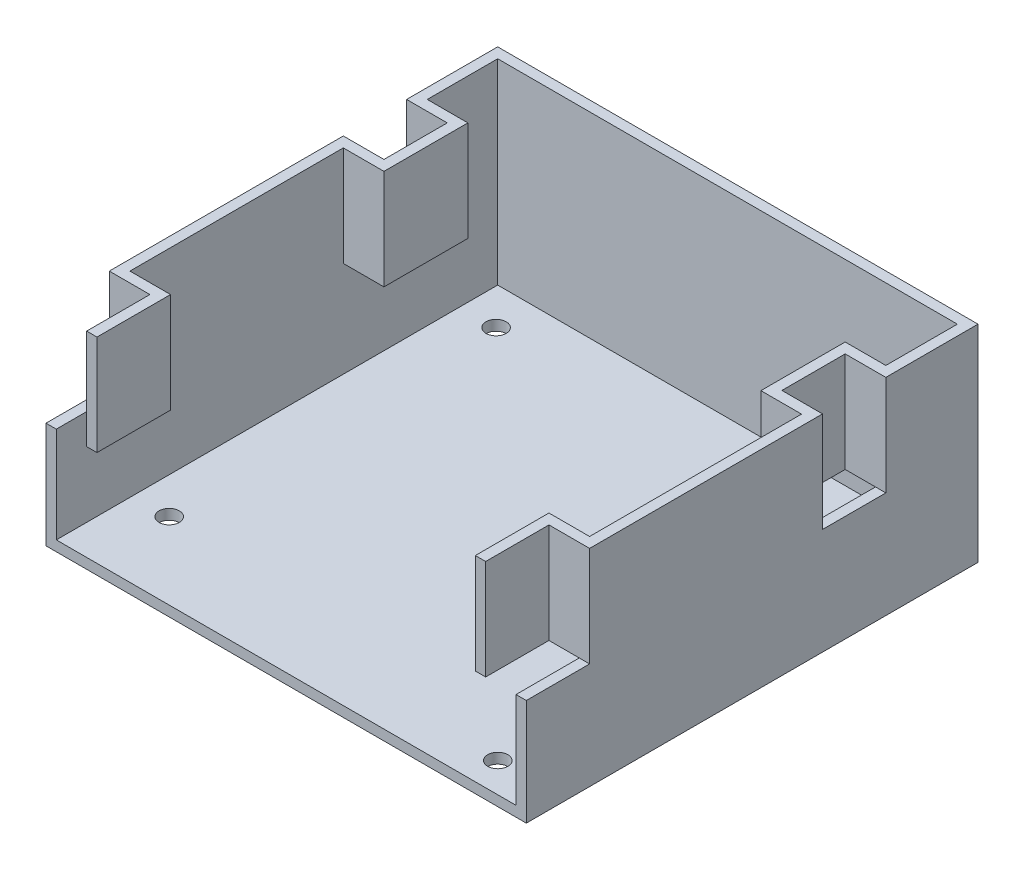
SolidWorks part; units mm, degrees
ref_plane "Front Plane" through (0, 0, 0) normal (0, 0, 1) x (1, 0, 0)
ref_plane "Top Plane" through (0, 0, 0) normal (0, 1, 0) x (1, 0, 0)
ref_plane "Right Plane" through (0, 0, 0) normal (1, 0, 0) x (0, 0, -1)
sketch "Sketch1" plane through (0, 0, 0) normal (0, 1, 0) x (1, 0, 0)
  line L1 (0, 0) -> (89.12, 0)
  line L2 (0, 0) -> (0, 85.57)
  line L3 (0, 85.57) -> (89.12, 85.57)
  line L4 (89.12, 0) -> (89.12, 85.57)
  dimension "D1" = 89.12
  dimension "D2" = 85.57
extrude "Boss-Extrude1" add sketch "Sketch1" along normal blind 2
sketch "Sketch3" plane through (0, 0, 0) normal (0, 0, 1) x (1, 0, 0)
  line L1 (0, 0) -> (-2, 0)
  line L2 (0, 0) -> (0, 30)
  line L3 (0, 30) -> (-2, 30)
  line L4 (-2, 0) -> (-2, 30)
  dimension "D1" = 2
  dimension "D2" = 30
extrude "Boss-Extrude2" add sketch "Sketch3" against normal blind 85.57
sketch "Sketch4" plane through (0, 0, 0) normal (0, 0, 1) x (1, 0, 0)
  line L1 (89.12, 0) -> (91.12, 0)
  line L2 (89.12, 0) -> (89.12, 30)
  line L3 (89.12, 30) -> (91.12, 30)
  line L4 (91.12, 0) -> (91.12, 30)
  dimension "D1" = 30
  dimension "D2" = 2
extrude "Boss-Extrude3" add sketch "Sketch4" against normal blind 85.57
sketch "Sketch5" plane through (0, 0, 0) normal (0, 1, 0) x (1, 0, 0)
  line L1 (-2, 85.57) -> (91.12, 85.57)
  line L2 (-2, 85.57) -> (-2, 87.57)
  line L3 (-2, 87.57) -> (91.12, 87.57)
  line L4 (91.12, 85.57) -> (91.12, 87.57)
  dimension "D1" = 2
extrude "Boss-Extrude4" add sketch "Sketch5" along normal blind 30
sketch "Sketch6" plane through (0, 0, 0) normal (0, 1, 0) x (1, 0, 0)
  line L0 (89.12, 0) -> (89.12, 5.755) construction
  line L1 (89.12, 0) -> (89.12, 85.57) construction
  line L2 (89.12, 5.755) -> (79.835, 5.755) construction
  line L3 (79.835, 5.755) -> (79.835, 0) construction
  line L4 (0, 0) -> (89.12, 0) construction
  circle A0 centre (79.835, 5.755) radius 1.96
  dimension "D3" = 3.92
extrude "Cut-Extrude2" cut sketch "Sketch6" along normal blind 30
sketch "Sketch7" plane through (0, 2, 0) normal (0, 1, 0) x (1, 0, 0)
  line L0 (89.12, 85.57) -> (82.285, 85.57) construction
  line L1 (0, 85.57) -> (89.12, 85.57) construction
  line L2 (82.285, 85.57) -> (82.285, 76.225) construction
  line L3 (82.285, 76.225) -> (89.12, 76.225) construction
  line L4 (89.12, 0) -> (89.12, 85.57) construction
  circle A0 centre (82.285, 76.225) radius 1.96
  dimension "D3" = 3.92
  dimension "D1" = 6.835
extrude "Cut-Extrude3" cut sketch "Sketch7" against normal blind 30
sketch "Sketch8" plane through (0, 0, 0) normal (0, 1, 0) x (1, 0, 0)
  line L0 (0, 85.57) -> (6.985, 85.57) construction
  line L1 (0, 85.57) -> (89.12, 85.57) construction
  line L2 (6.985, 85.57) -> (6.985, 78.28) construction
  line L3 (6.985, 78.28) -> (0, 78.28) construction
  line L4 (0, 85.57) -> (0, 0) construction
  circle A0 centre (6.985, 78.28) radius 1.96
  dimension "D3" = 3.92
extrude "Cut-Extrude4" cut sketch "Sketch8" along normal blind 30
sketch "Sketch9" plane through (0, 2, 0) normal (0, 1, 0) x (1, 0, 0)
  line L0 (0, 0) -> (0, 14.85) construction
  line L1 (0, 85.57) -> (0, 0) construction
  line L2 (0, 14.85) -> (7.035, 14.85) construction
  line L3 (7.035, 14.85) -> (7.035, 0) construction
  line L4 (0, 0) -> (89.12, 0) construction
  circle A0 centre (7.035, 14.85) radius 1.96
  dimension "D3" = 3.92
  dimension "D1" = 14.85
extrude "Cut-Extrude5" cut sketch "Sketch9" against normal blind 30
sketch "Sketch10" plane through (89.12, 0, 0) normal (-1, 0, 0) x (0, 0, 1)
  line L0 (0, 2) -> (0, 20.6) construction
  line L1 (0, 30) -> (0, 2) construction
  line L2 (0, 20.6) -> (-32.6241, 20.6) construction
  line L3 (-32.6241, 20.6) -> (-32.6241, 2) construction
  line L4 (0, 2) -> (-85.57, 2) construction
  line L5 (-32.6241, 20.6) -> (-32.6241, 30) construction
  line L6 (-85.57, 30) -> (0, 30) construction
  dimension "D1" = 18.6
sketch "Sketch11" plane through (0, 30, 0) normal (0, 1, 0) x (1, 0, 0)
  line L1 (89.12, 0) -> (83.24, 0)
  line L2 (89.12, 0) -> (89.12, 12.27)
  line L3 (89.12, 12.27) -> (83.24, 12.27)
  line L4 (83.24, 0) -> (83.24, 12.27)
  line L5 (83.24, 0) -> (81.24, 0)
  line L6 (83.24, 0) -> (83.24, 12.27)
  line L7 (83.24, 12.27) -> (81.24, 12.27)
  line L8 (81.24, 0) -> (81.24, 12.27)
  line L9 (81.24, 12.27) -> (89.12, 12.27)
  line L10 (81.24, 12.27) -> (81.24, 14.27)
  line L11 (81.24, 14.27) -> (89.12, 14.27)
  line L12 (89.12, 12.27) -> (89.12, 14.27)
  line M8 (89.12, 85.57) -> (89.12, 0)
  dimension "D1" = 5.88
  dimension "D2" = 12.27
  dimension "D3" = 2
  dimension "D4" = 2
extrude "Boss-Extrude5" add sketch "Sketch11" against normal blind 9.4 contours L11 L10 L7 L3 M8 | L8 L5 L4 L7 region at (82.24, 30, -6.135) region at (85.18, 30, -13.27)
sketch "Sketch12" plane through (0, 30, 0) normal (0, 1, 0) x (1, 0, 0)
  line L1 (89.12, 12.27) -> (91.12, 12.27)
  line L2 (89.12, 12.27) -> (89.12, 0)
  line L3 (89.12, 0) -> (91.12, 0)
  line L4 (91.12, 12.27) -> (91.12, 0)
extrude "Cut-Extrude6" cut sketch "Sketch12" against normal blind 9.4
sketch "Sketch13" plane through (0, 30, 0) normal (0, 1, 0) x (1, 0, 0)
  line L0 (89.12, 85.57) -> (89.12, 57.43) construction
  line L1 (89.12, 85.57) -> (89.12, 14.27) construction
  line L3 (89.12, 57.43) -> (83.24, 57.43)
  line L4 (89.12, 57.43) -> (89.12, 69.7)
  line L5 (89.12, 69.7) -> (83.24, 69.7)
  line L6 (83.24, 57.43) -> (83.24, 69.7)
  line L7 (83.24, 69.7) -> (81.24, 69.7)
  line L8 (83.24, 69.7) -> (83.24, 57.43)
  line L9 (83.24, 57.43) -> (81.24, 57.43)
  line L10 (81.24, 69.7) -> (81.24, 57.43)
  line L11 (81.24, 57.43) -> (89.12, 57.43)
  line L12 (81.24, 57.43) -> (81.24, 55.3598)
  line L13 (81.24, 55.3598) -> (89.12, 55.3598)
  line L14 (89.12, 57.43) -> (89.12, 55.3598)
  line L15 (81.24, 69.7) -> (89.12, 69.7)
  line L16 (81.24, 69.7) -> (81.24, 71.7)
  line L17 (81.24, 71.7) -> (89.12, 71.7)
  line L18 (89.12, 69.7) -> (89.12, 71.7)
  line M25 (89.12, 85.57) -> (89.12, 14.27)
  dimension "D1" = 28.14
  dimension "D2" = 12.27
  dimension "D3" = 5.88
  dimension "D4" = 2
  dimension "D5" = 2.0702
  dimension "D6" = 2
extrude "Boss-Extrude6" add sketch "Sketch13" against normal blind 9.4 contours L17 L16 L7 L5 M25 | L7 L10 L9 L6 | L12 L13 L3 L9 M25 region at (85.18, 30, -56.3949) region at (82.24, 30, -63.565) region at (85.18, 30, -70.7)
sketch "Sketch14" plane through (0, 30, 0) normal (0, 1, 0) x (1, 0, 0)
  line L0 (91.12, 87.57) -> (91.12, 12.27) construction
  line L1 (89.12, 69.7) -> (91.12, 69.7)
  line L2 (89.12, 69.7) -> (89.12, 57.43)
  line L3 (89.12, 57.43) -> (91.12, 57.43)
  line L4 (91.12, 69.7) -> (91.12, 57.43)
extrude "Cut-Extrude7" cut sketch "Sketch14" against normal blind 9.4
sketch "Sketch15" plane through (0, 30, 0) normal (0, 1, 0) x (1, 0, 0)
  line L0 (0, 85.57) -> (0, 57.64) construction
  line L1 (0, 85.57) -> (0, 0) construction
  line L3 (0, 57.64) -> (5.88, 57.64)
  line L4 (0, 57.64) -> (0, 69.91)
  line L5 (0, 69.91) -> (5.88, 69.91)
  line L6 (5.88, 57.64) -> (5.88, 69.91)
  line L7 (5.88, 69.91) -> (7.88, 69.91)
  line L8 (5.88, 69.91) -> (5.88, 57.64)
  line L9 (5.88, 57.64) -> (7.88, 57.64)
  line L10 (7.88, 69.91) -> (7.88, 57.64)
  line L11 (0, 57.64) -> (7.88, 57.64)
  line L12 (0, 57.64) -> (0, 55.64)
  line L13 (0, 55.64) -> (7.88, 55.64)
  line L14 (7.88, 57.64) -> (7.88, 55.64)
  line L15 (0, 69.91) -> (7.88, 69.91)
  line L16 (0, 69.91) -> (0, 71.91)
  line L17 (0, 71.91) -> (7.88, 71.91)
  line L18 (7.88, 69.91) -> (7.88, 71.91)
  line M12 (0, 0) -> (0, 85.57)
  dimension "D1" = 27.93
  dimension "D2" = 5.88
  dimension "D3" = 12.27
  dimension "D4" = 2
  dimension "D5" = 2
  dimension "D6" = 2
extrude "Boss-Extrude7" add sketch "Sketch15" against normal blind 9.4 contours L7 L18 L17 L5 M12 | L10 L7 L6 L9 | L14 L9 L3 L13 M12 region at (3.94, 30, -56.64) region at (6.88, 30, -63.775) region at (3.94, 30, -70.91)
sketch "Sketch16" plane through (0, 30, 0) normal (0, 1, 0) x (1, 0, 0)
  line L0 (-2, 87.57) -> (-2, 0) construction
  line L1 (-2, 69.91) -> (0, 69.91)
  line L2 (-2, 69.91) -> (-2, 57.64)
  line L3 (-2, 57.64) -> (0, 57.64)
  line L4 (0, 69.91) -> (0, 57.64)
extrude "Cut-Extrude8" cut sketch "Sketch16" against normal blind 9.4
sketch "Sketch17" plane through (0, 30, 0) normal (0, 1, 0) x (1, 0, 0)
  line L0 (0, 0) -> (89.12, 0) construction
  line L1 (0, 0) -> (5.88, 0)
  line L2 (0, 0) -> (0, 12.27)
  line L3 (0, 12.27) -> (5.88, 12.27)
  line L4 (5.88, 0) -> (5.88, 12.27)
  line L5 (5.88, 12.27) -> (7.88, 12.27)
  line L6 (5.88, 12.27) -> (5.88, 0)
  line L7 (5.88, 0) -> (7.88, 0)
  line L8 (7.88, 12.27) -> (7.88, 0)
  line L9 (0, 55.64) -> (0, 0) construction
  line L10 (7.88, 12.27) -> (0, 12.27)
  line L11 (7.88, 12.27) -> (7.88, 14.27)
  line L12 (7.88, 14.27) -> (0, 14.27)
  line L13 (0, 12.27) -> (0, 14.27)
  line M13 (0, 0) -> (0, 55.64)
  dimension "D1" = 12.27
  dimension "D2" = 5.88
  dimension "D3" = 2
  dimension "D4" = 2
extrude "Boss-Extrude8" add sketch "Sketch17" against normal blind 9.4 contours L11 L12 L3 L5 M13 | L8 L5 L4 L7 region at (6.88, 30, -6.135) region at (3.94, 30, -13.27)
sketch "Sketch18" plane through (0, 30, 0) normal (0, 1, 0) x (1, 0, 0)
  line L0 (-2, 57.64) -> (-2, 0) construction
  line L1 (0, 0) -> (-2, 0)
  line L2 (0, 0) -> (0, 12.27)
  line L3 (0, 12.27) -> (-2, 12.27)
  line L4 (-2, 0) -> (-2, 12.27)
extrude "Cut-Extrude9" cut sketch "Sketch18" against normal blind 9.4
sketch "Sketch19" plane through (0, 30, 0) normal (0, 1, 0) x (1, 0, 0)
  line L0 (83.24, 0) -> (81.24, 0)
  line L1 (81.24, 0) -> (81.24, 14.27)
  line L2 (81.24, 0) -> (81.24, 14.27) construction
  line L3 (81.24, 14.27) -> (89.12, 14.27)
  line L4 (89.12, 14.27) -> (89.12, 55.3598)
  line L5 (89.12, 55.3598) -> (81.24, 55.3598)
  line L6 (81.24, 55.3598) -> (81.24, 71.7)
  line L7 (81.24, 71.7) -> (89.12, 71.7)
  line L8 (89.12, 71.7) -> (89.12, 85.57)
  line L9 (89.12, 85.57) -> (0, 85.57)
  line L10 (0, 85.57) -> (0, 71.91)
  line L11 (0, 71.91) -> (7.88, 71.91)
  line L12 (7.88, 71.91) -> (7.88, 55.64)
  line L13 (7.88, 55.64) -> (0, 55.64)
  line L14 (0, 55.64) -> (0, 14.27)
  line L15 (0, 14.27) -> (7.88, 14.27)
  line L16 (7.88, 14.27) -> (7.88, 0)
  line L17 (7.88, 0) -> (5.88, 0)
  line L18 (5.88, 0) -> (5.88, 12.27)
  line L19 (5.88, 12.27) -> (-2, 12.27)
  line L20 (-2, 12.27) -> (-2, 57.64)
  line L21 (-2, 57.64) -> (5.88, 57.64)
  line L22 (5.88, 57.64) -> (5.88, 69.91)
  line L23 (5.88, 69.91) -> (-2, 69.91)
  line L24 (-2, 69.91) -> (-2, 87.57)
  line L25 (-2, 87.57) -> (91.12, 87.57)
  line L26 (91.12, 87.57) -> (91.12, 69.7)
  line L27 (91.12, 69.7) -> (83.24, 69.7)
  line L28 (83.24, 69.7) -> (83.24, 57.43)
  line L29 (83.24, 57.43) -> (91.12, 57.43)
  line L30 (91.12, 57.43) -> (91.12, 12.27)
  line L31 (91.12, 12.27) -> (83.24, 12.27)
  line L32 (83.24, 12.27) -> (83.24, 0)
extrude "Boss-Extrude9" add sketch "Sketch19" along normal blind 10
equation "\"tol1\"= 0.1cm"
equation "\"D1@Sketch1\"=8.812cm +\"tol1\""
equation "\"D2@Sketch1\"=8.457cm +\"tol1\""
equation "\"D1@Boss-Extrude2\"=8.457 +\"tol1\""
equation "\"D1@Boss-Extrude3\"=8.457 +\"tol1\""
equation "\"D1@Sketch6\"=0.5255 + \"tol2\""
equation "\"hole\"= 0.392cm"
equation "\"D3@Sketch6\"=\"hole\""
equation "\"tol2\"= \"tol1\" / 2"
equation "\"D2@Sketch6\"=0.8785 + \"tol2\""
equation "\"D2@Sketch9\"=0.6535 + \"tol2\""
equation "\"D3@Sketch9\"=\"hole\""
equation "\"D1@Sketch9\"=1.435 + \"tol2\""
equation "\"D2@Sketch8\"=0.6485 + \"tol2\""
equation "\"D1@Sketch8\"=0.679 + \"tol2\""
equation "\"D3@Sketch8\"=\"hole\""
equation "\"D3@Sketch7\"=\"hole\""
equation "\"D2@Sketch7\"=0.8845 + \"tol2\""
equation "\"D1@Sketch7\"=0.6335 + \"tol2\""
equation "\"heightTol\"= 0.5cm"
equation "\"D1@Sketch10\"=1.36 + \"heightTol\""
